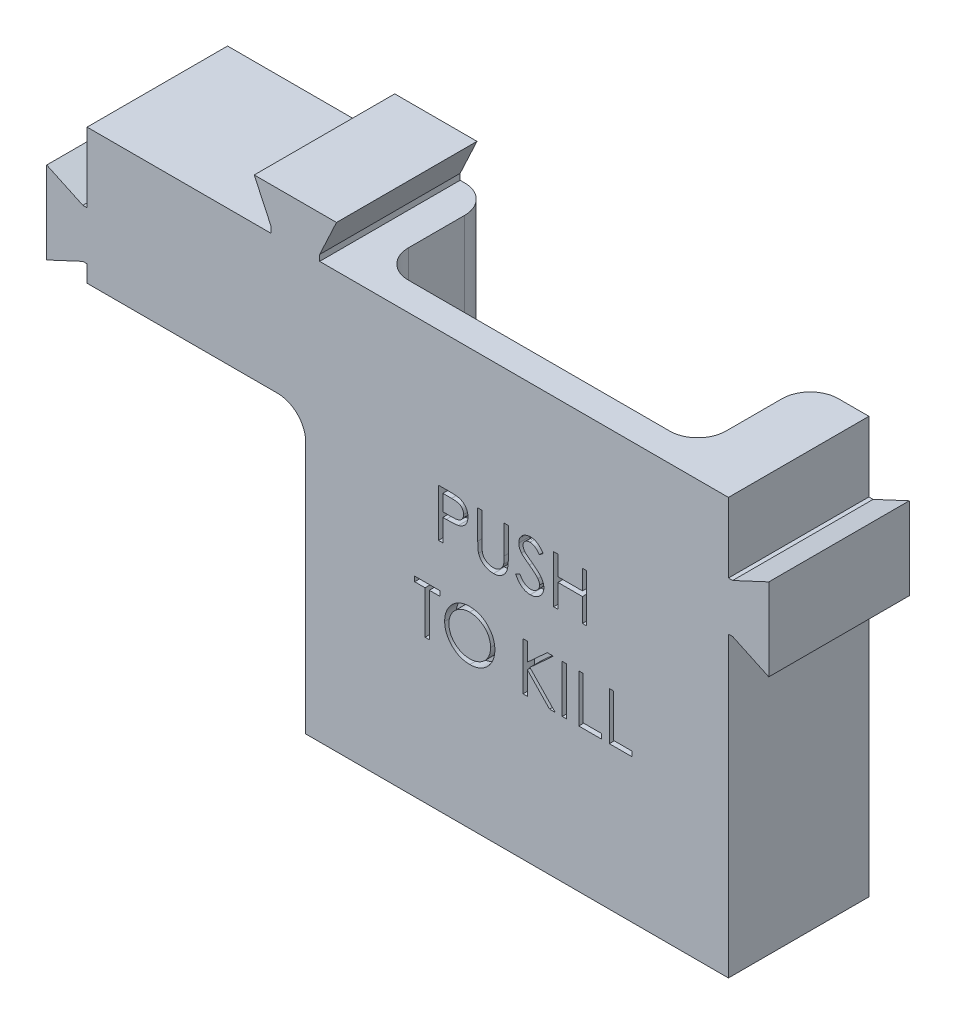
SolidWorks part; units mm, degrees
ref_plane "Front Plane" through (0, 0, 0) normal (0, 0, 1) x (1, 0, 0)
ref_plane "Top Plane" through (0, 0, 0) normal (0, 1, 0) x (1, 0, 0)
ref_plane "Right Plane" through (0, 0, 0) normal (1, 0, 0) x (0, 0, -1)
sketch "Sketch1" plane through (0, 0, 0) normal (0, 0, 1) x (1, 0, 0)
  line L6 (4.03, 97.409) -> (20.6653, 97.409)
  line L7 (20.6653, 97.409) -> (20.6653, 97.951)
  line L8 (25.0547, 97.409) -> (25.0547, 97.951)
  line L9 (26.5786, 101.219) -> (25.0547, 97.951)
  line L10 (19.1414, 101.219) -> (26.5786, 101.219)
  line L11 (20.6653, 97.951) -> (19.1414, 101.219)
  line L12 (26.5786, 101.219) -> (25.0547, 97.951)
  line L13 (19.1414, 101.219) -> (26.5786, 101.219)
  line L14 (20.6653, 97.951) -> (19.1414, 101.219)
  line L15 (3.81, 97.79) -> (20.32, 97.79) construction
  line L36 (3.649, 86.7053) -> (0.381, 85.1814)
  line L37 (0.381, 85.1814) -> (0.381, 92.6186)
  line L38 (0.381, 92.6186) -> (3.649, 91.0947)
  line L39 (3.649, 86.7053) -> (0.381, 85.1814)
  line L40 (0.381, 85.1814) -> (0.381, 92.6186)
  line L41 (0.381, 92.6186) -> (3.649, 91.0947)
  line L57 (3.649, 86.7053) -> (4.03, 86.7053)
  line L58 (4.03, 86.7053) -> (4.03, 85.1814)
  line L59 (4.03, 85.1814) -> (62.01, 85.1814)
  line L60 (65.659, 85.1814) -> (62.391, 86.7053)
  line L61 (65.659, 92.6186) -> (65.659, 85.1814)
  line L62 (62.391, 91.0947) -> (65.659, 92.6186)
  line L63 (65.659, 85.1814) -> (62.391, 86.7053)
  line L64 (65.659, 92.6186) -> (65.659, 85.1814)
  line L65 (62.391, 91.0947) -> (65.659, 92.6186)
  line L66 (62.01, 85.1814) -> (62.01, 86.7053)
  line L67 (62.01, 86.7053) -> (62.391, 86.7053)
  line L68 (3.649, 91.0947) -> (4.03, 91.0947)
  line L69 (4.03, 91.0947) -> (4.03, 97.409)
  line L71 (62.01, 97.409) -> (62.01, 91.0947)
  line L72 (62.01, 91.0947) -> (62.391, 91.0947)
  line L76 (25.0547, 97.409) -> (62.01, 97.409)
  dimension "D4" = 0.381
  dimension "D5" = 0.381
  dimension "D1" = 0.381
  dimension "D2" = 0.381
  dimension "D3" = 0.381
extrude "Boss-Extrude1" add sketch "Sketch1" along normal blind 12.7
sketch "Sketch2" plane through (0, 85.1814, 0) normal (0, -1, 0) x (1, 0, 0)
  line L0 (4.03, 0) -> (62.01, 0) construction
  line L1 (28.0035, 0) -> (56.7055, 0)
  line L2 (28.0035, 0) -> (28.0035, 10.16)
  line L3 (28.0035, 10.16) -> (56.7055, 10.16)
  line L4 (56.7055, 0) -> (56.7055, 10.16)
  line L7 (31.8135, -0.9884) -> (31.8135, -13.1804) construction
  line L8 (52.8955, -0.9884) -> (52.8955, -13.1804) construction
  line L9 (4.03, 12.7) -> (62.01, 12.7) construction
  dimension "D1" = 3.81
  dimension "D2" = 3.81
  dimension "D3" = 2.54
extrude "Cut-Extrude1" cut sketch "Sketch2" against normal through all
fillet "Fillet1" radius 2.54 4 edges at (56.7055, 91.2952, 0) (28.0035, 91.2952, 0) (28.0035, 91.2952, 10.16) (56.7055, 91.2952, 10.16)
sketch "Sketch3" plane through (0, 85.1814, 0) normal (0, -1, 0) x (1, 0, 0)
  line L0 (4.03, 0) -> (25.4635, 0) construction
  line L1 (23.7939, 0) -> (62.01, 0)
  line L2 (23.7939, 0) -> (23.7939, 12.7)
  line L3 (23.7939, 12.7) -> (62.01, 12.7)
  line L4 (62.01, 0) -> (62.01, 12.7)
  line L20 (56.7055, 7.62) -> (56.7055, 2.54)
  line L21 (30.5435, 10.16) -> (54.1655, 10.16)
  line L22 (28.0035, 2.54) -> (28.0035, 7.62)
  line L23 (56.7055, 7.62) -> (56.7055, 2.54)
  line L24 (30.5435, 10.16) -> (54.1655, 10.16)
  line L25 (28.0035, 2.54) -> (28.0035, 7.62)
  arc A20 (56.7055, 2.54) -> (59.2455, 0) centre (59.2455, 2.54) ccw
  arc A21 (56.7055, 7.62) -> (54.1655, 10.16) centre (54.1655, 7.62) ccw
  arc A22 (30.5435, 10.16) -> (28.0035, 7.62) centre (30.5435, 7.62) ccw
  arc A23 (25.4635, 0) -> (28.0035, 2.54) centre (25.4635, 2.54) ccw
  arc A24 (56.7055, 2.54) -> (59.2455, 0) centre (59.2455, 2.54) ccw
  arc A25 (56.7055, 7.62) -> (54.1655, 10.16) centre (54.1655, 7.62) ccw
  arc A26 (30.5435, 10.16) -> (28.0035, 7.62) centre (30.5435, 7.62) ccw
  arc A27 (25.4635, 0) -> (28.0035, 2.54) centre (25.4635, 2.54) ccw
  line M12 (56.7055, 7.62) -> (56.7055, 2.54)
  arc M13 (56.7055, 2.54) -> (59.2455, 0) centre (59.2455, 2.54) ccw
  line M14 (59.2455, 0) -> (62.01, 0)
  line M15 (62.01, 0) -> (62.01, 12.7)
  line M16 (62.01, 12.7) -> (4.03, 12.7)
  line M18 (4.03, 0) -> (25.4635, 0)
  arc M19 (25.4635, 0) -> (28.0035, 2.54) centre (25.4635, 2.54) ccw
  line M20 (28.0035, 2.54) -> (28.0035, 7.62)
  arc M21 (28.0035, 7.62) -> (30.5435, 10.16) centre (30.5435, 7.62) cw
  line M22 (30.5435, 10.16) -> (54.1655, 10.16)
  arc M23 (54.1655, 10.16) -> (56.7055, 7.62) centre (54.1655, 7.62) cw
  dimension "D1" = 0
extrude "Boss-Extrude2" add sketch "Sketch3" along normal blind 25.4 contours L2 M18 M19 M20 M21 M22 M23 M12 M13 M14 M15 M16 region at (24.1966, 85.1814, 6.35)
fillet "Fillet2" radius 2.54 1 edges at (23.7939, 85.1814, 6.35)
sketch "Sketch4" plane through (0, 0, 12.7) normal (0, 0, 1) x (1, 0, 0)
  text T0 " PUSH\r\nTO KILL" font "Century Gothic" height 4.318
extrude "Cut-Extrude2" cut sketch "Sketch4" against normal blind 1.016
